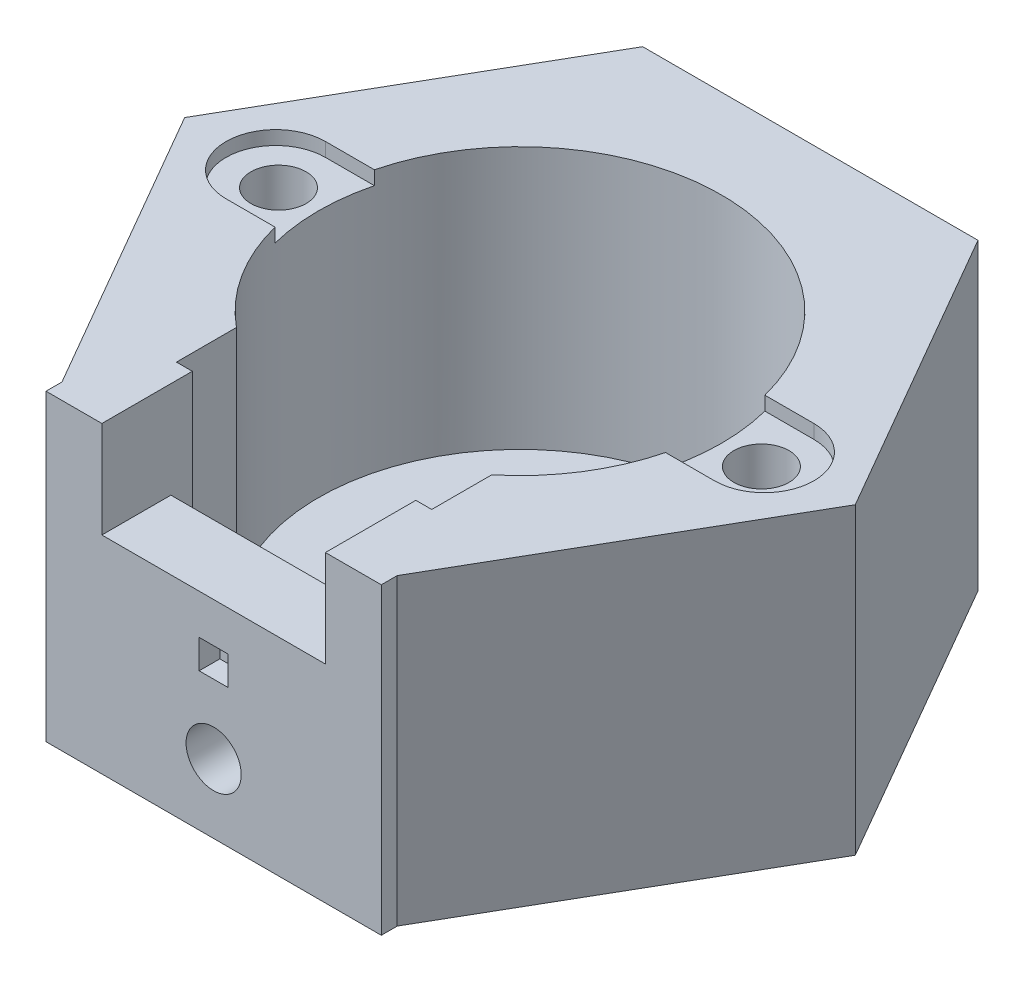
SolidWorks part; units mm, degrees
ref_plane "Front Plane" through (0, 0, 0) normal (0, 0, 1) x (1, 0, 0)
ref_plane "Top Plane" through (0, 0, 0) normal (0, 1, 0) x (1, 0, 0)
ref_plane "Right Plane" through (0, 0, 0) normal (1, 0, 0) x (0, 0, -1)
sketch "Sketch1" plane through (0, 0, 0) normal (0, 1, 0) x (1, 0, 0)
  line L0 (-33.6669, 0) -> (32.8036, 0) construction
  line L1 (0, 37.5104) -> (0, -35.9484) construction
  line L2 (-17.7, 3.6) -> (-14.1492, 3.6)
  line L3 (-17.7, -3.6) -> (-14.1492, -3.6)
  line L4 (14.1492, 3.6) -> (17.7, 3.6)
  line L5 (24.3, 0) -> (12.15, 21.0444)
  line L6 (12.15, 21.0444) -> (-12.15, 21.0444)
  line L7 (-12.15, 21.0444) -> (-24.3, 0)
  line L8 (-24.3, 0) -> (-12.15, -21.0444)
  line L9 (-12.15, -21.0444) -> (12.15, -21.0444)
  line L10 (12.15, -21.0444) -> (24.3, 0)
  line L12 (-8.1, -12.147) -> (-8.1, -22.2)
  line L13 (-8.1, -22.2) -> (8.1, -22.2)
  line L14 (8.1, -12.147) -> (8.1, -22.2)
  line L19 (14.1492, -3.6) -> (17.7, -3.6)
  line L20 (-8.1, -17.2) -> (8.1, -17.2)
  line L22 (-12.15, -22.2) -> (12.15, -22.2)
  line L23 (-12.15, -22.2) -> (-12.15, -21.0444)
  line L24 (-12.15, -21.0444) -> (12.15, -21.0444)
  line L25 (12.15, -22.2) -> (12.15, -21.0444)
  line L26 (-9.25, 0) -> (9.25, 0)
  line L27 (-9.25, 0) -> (-9.25, -15.647)
  line L28 (-9.25, -15.647) -> (9.25, -15.647)
  line L29 (9.25, 0) -> (9.25, -15.647)
  arc A0 (8.1, -12.147) -> (-8.1, -12.147) centre (0, 0) ccw
  arc A1 (17.7, -3.6) -> (17.7, 3.6) centre (17.7, 0) ccw
  arc A2 (-17.7, -3.6) -> (-17.7, 3.6) centre (-17.7, 0) cw
  circle A5 centre (0, 0) radius 21.0444 construction
  circle A6 centre (17.5, 0) radius 2
  circle A7 centre (-17.5, 0) radius 2
  dimension "D1" = 29.2
  dimension "D2" = 7.2
  dimension "D3" = 4
  dimension "D5" = 3
  dimension "D7" = 5
  dimension "D4" = 35.4
  dimension "D6" = 16.2
  dimension "D8" = 18.5
  dimension "D9" = 35
  dimension "D10" = 17.2
  dimension "D11" = 3.5
extrude "Boss-Extrude12" add sketch "Sketch1" along normal blind 22 contours L3 A2 L2 A0 L4 A1 L19 L14 L9 L10 L5 L6 L7 L8 L12 region at (-21.9429, 0, 0)
extrude "Boss-Extrude13" add sketch "Sketch1<14>" along normal blind 21 contours L19 A1 L4 A0 A6 | A2 L3 A0 L2 A7 region at (-15.9246, 0, -3.4985) region at (15.9246, 0, -3.4985)
sketch "Sketch1<14>" plane through (0, 0, 0) normal (0, 1, 0) x (1, 0, 0) same geometry as "Sketch1"
extrude "Boss-Extrude14" add sketch "Sketch1<15>" along normal blind 3 contours A0 region at (0, 0, -4.077)
sketch "Sketch1<15>" plane through (0, 0, 0) normal (0, 1, 0) x (1, 0, 0) same geometry as "Sketch1"
extrude "Boss-Extrude15" add sketch "Sketch1<16>" along normal blind 3 contours A0 L12 L20 L14 region at (0, 0, 16.4235)
sketch "Sketch1<16>" plane through (0, 0, 0) normal (0, 1, 0) x (1, 0, 0) same geometry as "Sketch1"
extrude "Boss-Extrude16" add sketch "Sketch1<17>" along normal blind 15 contours L20 L12 L9 L14 region at (0, 0, 19.1222)
sketch "Sketch1<17>" plane through (0, 0, 0) normal (0, 1, 0) x (1, 0, 0) same geometry as "Sketch1"
extrude "Boss-Extrude17" add sketch "Sketch1<18>" along normal blind 18 contours A6 | A7 region at (17.5, 0, 0) region at (-17.5, 0, 0)
sketch "Sketch1<18>" plane through (0, 0, 0) normal (0, 1, 0) x (1, 0, 0) same geometry as "Sketch1"
extrude "Boss-Extrude18" add sketch "Sketch1<19>" along normal blind 22 contours L23 L22 L12 L9 | L22 L25 L9 L14 region at (-10.125, 0, 21.6222) region at (10.125, 0, 21.6222)
sketch "Sketch1<19>" plane through (0, 0, 0) normal (0, 1, 0) x (1, 0, 0) same geometry as "Sketch1"
extrude "Boss-Extrude19" add sketch "Sketch1<20>" along normal blind 15 contours L14 L9 L12 L13 region at (0, 0, 21.6222)
sketch "Sketch1<20>" plane through (0, 0, 0) normal (0, 1, 0) x (1, 0, 0) same geometry as "Sketch1"
sketch "Sketch10" plane through (0, 0, 22.2) normal (0, 0, 1) x (1, 0, 0)
  line L0 (0, 36.7435) -> (0, -17.2864) construction
  line L2 (-12.15, 0) -> (12.15, 0) construction
  line L3 (-1.05, 12.1) -> (1.05, 12.1)
  line L4 (-1.05, 12.1) -> (-1.05, 10)
  line L5 (-1.05, 10) -> (1.05, 10)
  line L6 (1.05, 12.1) -> (1.05, 10)
  circle A0 centre (0, 5) radius 2
  dimension "D1" = 4
  dimension "D2" = 3
  dimension "D3" = 3
  dimension "D4" = 2.1
  dimension "D5" = 2.1
extrude "Cut-Extrude6" cut sketch "Sketch10" against normal blind 3 contours A0
extrude "Cut-Extrude7" cut sketch "Sketch10<10>" against normal blind 1.5 contours L5 L6 L3 L4
sketch "Sketch10<10>" plane through (0, 0, 22.2) normal (0, 0, 1) x (1, 0, 0) same geometry as "Sketch10"
extrude "Boss-Extrude20" add sketch "Sketch1<21>" along normal blind 3 contours L14 A0 L29 L26 L27 L12 L28 | A0 L27 L28 L12 | A0 L14 L28 L29 region at (-8.6958, 0, 13.6838) region at (0, 0, 7.6356) region at (8.6958, 0, 13.6838)
sketch "Sketch1<21>" plane through (0, 0, 0) normal (0, 1, 0) x (1, 0, 0) same geometry as "Sketch1"
